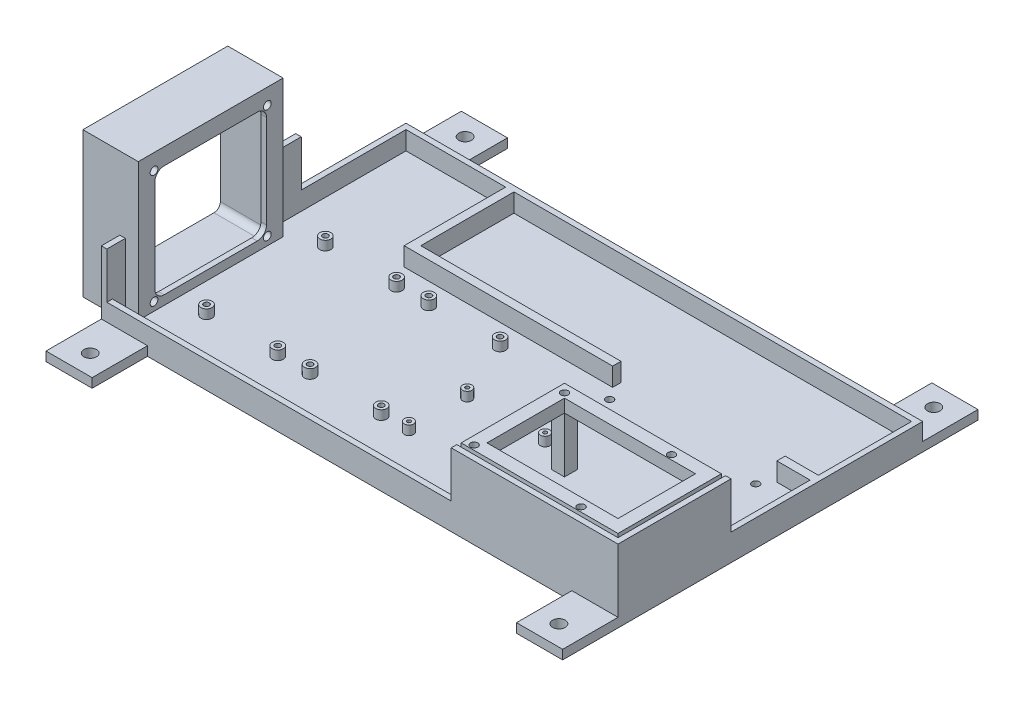
SolidWorks part; units mm, degrees
ref_plane "Front Plane" through (0, 0, 0) normal (0, 0, 1) x (1, 0, 0)
ref_plane "Top Plane" through (0, 0, 0) normal (0, 1, 0) x (1, 0, 0)
ref_plane "Right Plane" through (0, 0, 0) normal (1, 0, 0) x (0, 0, -1)
sketch "Sketch1" plane through (0, 0, 0) normal (0, 1, 0) x (1, 0, 0)
  line L1 (-140, -82.55) -> (140, -82.55)
  line L2 (-140, -82.55) -> (-140, 82.55)
  line L3 (-140, 82.55) -> (140, 82.55)
  line L4 (140, -82.55) -> (140, 82.55)
  line L5 (-140, -82.55) -> (140, 82.55) construction
  line L6 (-140, 82.55) -> (140, -82.55) construction
  point P0 (0, 0)
  dimension "D1" = 165.1
  dimension "D2" = 280
extrude "Floor" add sketch "Sketch1" along normal blind 4.3805
sketch "Sketch2" plane through (0, 4.3805, 0) normal (0, 1, 0) x (1, 0, 0)
  line L0 (137, -79.55) -> (137, 79.55)
  line L1 (137, 79.55) -> (-137, 79.55)
  line L2 (-137, 79.55) -> (-137, -79.55)
  line L3 (-137, -79.55) -> (137, -79.55)
  line L4 (140, -82.55) -> (140, 82.55)
  line L5 (140, 82.55) -> (-140, 82.55)
  line L6 (-140, 82.55) -> (-140, -82.55)
  line L7 (-140, -82.55) -> (140, -82.55)
  line L8 (140, -82.55) -> (140, 82.55)
  line L9 (140, 82.55) -> (-140, 82.55)
  line L10 (-140, 82.55) -> (-140, -82.55)
  line L11 (-140, -82.55) -> (140, -82.55)
  dimension "D1" = 0
  dimension "D2" = 3
extrude "Wall" add sketch "Sketch2" along normal blind 10
sketch "Sketch4" plane through (0, 4.3805, 0) normal (0, 1, 0) x (1, 0, 0)
  line L0 (130, -30.55) -> (59, -30.55)
  line L1 (137, -79.55) -> (52, -79.55)
  line L2 (137, -79.55) -> (137, -23.55)
  line L3 (137, -23.55) -> (52, -23.55)
  line L4 (52, -79.55) -> (52, -23.55)
  line L5 (59, -72.55) -> (59, -30.55)
  line L6 (130, -72.55) -> (59, -72.55)
  line L7 (130, -72.55) -> (130, -30.55)
  dimension "D1" = 85
  dimension "D2" = 56
  dimension "D3" = 7
extrude "Rpi stand" add sketch "Sketch4" along normal blind 7 from offset 30
sketch "Sketch7" plane through (0, 14.3805, 0) normal (0, 1, 0) x (1, 0, 0)
  line L0 (-137, 79.55) -> (-137, -79.55) construction
  line L1 (-140, -82.55) -> (-137, -82.55)
  line L2 (-140, -82.55) -> (-140, 22.7839)
  line L3 (-140, 22.7839) -> (-137, 22.7839)
  line L4 (-137, -82.55) -> (-137, 22.7839)
  line L5 (-137, -79.55) -> (137, -79.55) construction
  line L6 (140, -82.55) -> (49.6123, -82.55)
  line L7 (140, -82.55) -> (140, -79.55)
  line L8 (137, -79.55) -> (49.6123, -79.55)
  line L9 (49.6123, -82.55) -> (49.6123, -79.55)
  line L10 (137, -79.55) -> (137, 79.55) construction
  line L12 (140, -79.55) -> (140, -21.3069)
  line L13 (140, -21.3069) -> (137, -21.3069)
  line L14 (137, -79.55) -> (137, -21.3069)
  line L15 (-137, -79.55) -> (137, -79.55) construction
extrude "Temp support" add sketch "Sketch7" along normal blind 25
sketch "Sketch3" plane through (0, 0, 0) normal (0, 1, 0) x (1, 0, 0)
  line L0 (-127, 101.6) -> (127, 101.6) construction
  line L1 (-140, 82.55) -> (-115, 82.55)
  line L2 (-140, 82.55) -> (-140, 112.55)
  line L3 (-140, 112.55) -> (-115, 112.55)
  line L4 (-115, 82.55) -> (-115, 112.55)
  line L5 (140, 82.55) -> (115, 82.55)
  line L6 (140, 82.55) -> (140, 112.55)
  line L7 (140, 112.55) -> (115, 112.55)
  line L8 (115, 82.55) -> (115, 112.55)
  line L9 (-140, -82.55) -> (-115, -82.55)
  line L10 (-140, -82.55) -> (-140, -112.55)
  line L11 (-140, -112.55) -> (-115, -112.55)
  line L12 (-115, -82.55) -> (-115, -112.55)
  line L13 (140, -82.55) -> (115, -82.55)
  line L14 (140, -82.55) -> (140, -112.55)
  line L15 (140, -112.55) -> (115, -112.55)
  line L16 (115, -82.55) -> (115, -112.55)
  line L17 (127, 101.6) -> (127, -101.6) construction
  line L18 (127, -101.6) -> (-127, -101.6) construction
  line L19 (-127, -101.6) -> (-127, 101.6) construction
  line L20 (-140, 30.6215) -> (140, 30.6215) construction
  line L22 (140, -21.3069) -> (140, 82.55) construction
  line L23 (0, 101.6) -> (0, -101.6) construction
  line L24 (-140, 22.7839) -> (-140, -82.55) construction
  line L25 (140, -21.3069) -> (140, 82.55) construction
  line L26 (-137, -82.55) -> (49.6123, -82.55) construction
  circle A0 centre (-127, 101.6) radius 3.429
  circle A1 centre (127, 101.6) radius 3.429
  circle A2 centre (127, -101.6) radius 3.429
  circle A3 centre (-127, -101.6) radius 3.429
  point P28 (-127.5, -82.55)
  point P29 (-115, -97.55)
  point P30 (127.5, -82.55)
  point P31 (-115, 97.55)
  dimension "D5" = 6.858
  dimension "D1" = 25
  dimension "D2" = 25
  dimension "D3" = 30
  dimension "D4" = 30
  dimension "D6" = 203.2
  dimension "D7" = 254
extrude "Brackets" add sketch "Sketch3" along normal blind 5
sketch "Sketch5" plane through (-140, 0, 0) normal (-1, 0, 0) x (0, 0, 1)
  line L0 (-5.95, 78.8805) -> (72.55, 78.8805)
  line L1 (1.55, 4.3805) -> (65.05, 4.3805)
  line L2 (-1.95, 7.8805) -> (-1.95, 71.3805)
  line L3 (1.55, 74.8805) -> (65.05, 74.8805)
  line L4 (68.55, 7.8805) -> (68.55, 71.3805)
  line L5 (72.55, 0.3805) -> (72.55, 78.8805)
  line L6 (-5.95, 0.3805) -> (72.55, 0.3805)
  line L7 (-5.95, 0.3805) -> (-5.95, 78.8805)
  line L8 (-1.95, 4.3805) -> (68.55, 4.3805) construction
  line L9 (112.55, 5) -> (112.55, 0) construction
  line L10 (-1.95, 4.3805) -> (-1.95, 74.8805) construction
  line L11 (-79.55, 4.3805) -> (79.55, 4.3805) construction
  line L12 (68.55, 4.3805) -> (68.55, 74.8805) construction
  line L13 (-1.95, 74.8805) -> (68.55, 74.8805) construction
  arc A0 (1.55, 4.3805) -> (-1.95, 7.8805) centre (1.55, 7.8805) cw
  arc A1 (65.05, 4.3805) -> (68.55, 7.8805) centre (65.05, 7.8805) ccw
  arc A2 (65.05, 74.8805) -> (68.55, 71.3805) centre (65.05, 71.3805) cw
  arc A3 (-1.95, 71.3805) -> (1.55, 74.8805) centre (1.55, 71.3805) cw
  dimension "D4" = 3.5
  dimension "D1" = 70.5
  dimension "D2" = 70.5
  dimension "D5" = 40
  dimension "D3" = 4
extrude "Fan Holder" add sketch "Sketch5" along normal blind 20 and the other way blind 10
sketch "Sketch8" plane through (-140, 0, 0) normal (-1, 0, 0) x (0, 0, 1)
  line L4 (-1.95, 39.3805) -> (-1.95, 7.8805)
  line L5 (1.55, 4.3805) -> (65.05, 4.3805)
  line L6 (68.55, 7.8805) -> (68.55, 39.3805)
  line L7 (68.55, 39.3805) -> (-1.95, 39.3805)
  line L8 (-1.95, 39.3805) -> (-1.95, 7.8805)
  line L9 (1.55, 4.3805) -> (65.05, 4.3805)
  line L10 (68.55, 7.8805) -> (68.55, 39.3805)
  line L15 (68.55, 39.3805) -> (-1.95, 39.3805)
  arc A2 (-1.95, 7.8805) -> (1.55, 4.3805) centre (1.55, 7.8805) ccw
  arc A3 (-1.95, 7.8805) -> (1.55, 4.3805) centre (1.55, 7.8805) ccw
  arc A4 (65.05, 4.3805) -> (68.55, 7.8805) centre (65.05, 7.8805) ccw
  arc A5 (65.05, 4.3805) -> (68.55, 7.8805) centre (65.05, 7.8805) ccw
  dimension "D1" = 0
extrude "Fan hole" cut sketch "Sketch8" against normal up to next (3 mm away)
sketch "Sketch11" plane through (-130, 0, 0) normal (-1, 0, 0) x (0, 0, 1)
  line L0 (-5.95, 39.6305) -> (72.55, 39.6305) construction
  line L1 (33.3, 78.8805) -> (33.3, 0.3805) construction
  line L3 (2.6, 8.9305) -> (64, 8.9305) construction
  line L4 (-5.95, 78.8805) -> (-5.95, 0.3805)
  line L5 (-5.95, 0.3805) -> (72.55, 0.3805)
  line L6 (72.55, 0.3805) -> (72.55, 78.8805)
  line L7 (72.55, 78.8805) -> (-5.95, 78.8805)
  line L8 (-5.95, 78.8805) -> (-5.95, 0.3805)
  line L9 (-5.95, 0.3805) -> (72.55, 0.3805)
  line L10 (72.55, 0.3805) -> (72.55, 78.8805)
  line L11 (72.55, 78.8805) -> (-5.95, 78.8805)
  line L12 (2.6, 8.9305) -> (2.6, 70.3305) construction
  line L13 (2.6, 70.3305) -> (64, 70.3305) construction
  line L14 (64, 8.9305) -> (64, 70.3305) construction
  line L15 (2.6, 8.9305) -> (64, 70.3305) construction
  line L16 (3.05, 69.8805) -> (3.05, 9.3805)
  line L17 (3.05, 9.3805) -> (63.55, 9.3805)
  line L18 (63.55, 9.3805) -> (63.55, 69.8805)
  line L19 (63.55, 69.8805) -> (3.05, 69.8805)
  line L20 (3.05, 64.8805) -> (3.05, 14.3805)
  line L21 (8.05, 9.3805) -> (58.55, 9.3805)
  line L22 (63.55, 14.3805) -> (63.55, 64.8805)
  line L23 (58.55, 69.8805) -> (8.05, 69.8805)
  line L24 (2.6, 70.3305) -> (64, 8.9305) construction
  arc A0 (3.05, 14.3805) -> (8.05, 9.3805) centre (8.05, 14.3805) ccw
  arc A1 (58.55, 9.3805) -> (63.55, 14.3805) centre (58.55, 14.3805) ccw
  arc A2 (63.55, 64.8805) -> (58.55, 69.8805) centre (58.55, 64.8805) ccw
  arc A3 (3.05, 64.8805) -> (8.05, 69.8805) centre (8.05, 64.8805) cw
  circle A4 centre (2.6, 70.3305) radius 2.1
  circle A5 centre (64, 70.3305) radius 2.1
  circle A6 centre (64, 8.9305) radius 2.1
  circle A7 centre (2.6, 8.9305) radius 2.1
  point P24 (33.3, 39.6305)
  point P33 (0, 0)
  point P34 (33.3, 39.6305)
  dimension "D3" = 5
  dimension "D6" = 4.2
  dimension "D4" = 61.4
  dimension "D5" = 61.4
  dimension "D1" = 0
  dimension "D2" = 9
extrude "Boss-Extrude9" add sketch "Sketch11" along normal blind 3
sketch "Sketch12" plane through (0, 34.3805, 0) normal (0, -1, 0) x (1, 0, 0)
  line L1 (52, 23.55) -> (59, 23.55)
  line L2 (52, 23.55) -> (52, 30.55)
  line L3 (52, 30.55) -> (59, 30.55)
  line L4 (59, 23.55) -> (59, 30.55)
  dimension "D1" = 7
  dimension "D2" = 7
extrude "Boss-Extrude10" add sketch "Sketch12" along normal up to next
sketch "Sketch13" plane through (0, 4.3805, 0) normal (0, 1, 0) x (1, 0, 0)
  line L0 (-137, -79.55) -> (137, -79.55) construction
  line L1 (-137, -82.55) -> (-137, -72.55) construction
  line L2 (-114, -51.55) -> (-114, 12.85) construction
  line L3 (-114, 12.85) -> (-75.4, 12.85) construction
  line L4 (-114, -51.55) -> (-75.4, -51.55) construction
  line L5 (-75.4, 12.85) -> (-75.4, -51.55) construction
  line L6 (-75.4, 12.85) -> (-57.9, 12.85) construction
  line L7 (-57.9, 12.85) -> (-57.9, -51.55) construction
  line L8 (-57.9, -51.55) -> (-19.3, -51.55) construction
  line L9 (-19.3, -51.55) -> (-19.3, 12.85) construction
  line L10 (-19.3, 12.85) -> (-57.9, 12.85) construction
  line L11 (-75.4, -51.55) -> (-57.9, -51.55) construction
  line L12 (-19.3, -51.55) -> (-4.3, -51.55) construction
  line L13 (-4.3, -51.55) -> (-4.3, -19.95) construction
  line L14 (-4.3, -19.95) -> (37.87, -19.95) construction
  line L15 (37.87, -19.95) -> (37.87, -51.55) construction
  line L16 (37.87, -51.55) -> (-4.3, -51.55) construction
  line L17 (111.34, 79.55) -> (111.34, 18.05) construction
  line L19 (137, 79.55) -> (-137, 79.55) construction
  line L20 (137, -21.3069) -> (137, 79.55) construction
  line L21 (111.34, 18.05) -> (114.04, 18.05) construction
  line L22 (111.34, 18.05) -> (34.84, 18.05) construction
  circle A0 centre (-114, -51.55) radius 1.5
  circle A1 centre (-114, 12.85) radius 1.5
  circle A2 centre (-75.4, 12.85) radius 1.5
  circle A3 centre (-75.4, -51.55) radius 1.5
  circle A4 centre (-57.9, 12.85) radius 1.5
  circle A5 centre (-57.9, -51.55) radius 1.5
  circle A6 centre (-19.3, -51.55) radius 1.5
  circle A7 centre (-19.3, 12.85) radius 1.5
  circle A8 centre (-4.3, -51.55) radius 1
  circle A9 centre (-4.3, -19.95) radius 1
  circle A10 centre (37.87, -19.95) radius 1
  circle A11 centre (37.87, -51.55) radius 1
  circle A12 centre (114.04, 18.05) radius 2
  circle A13 centre (34.84, 18.05) radius 2
  circle A14 centre (-114, 12.85) radius 3
  circle A15 centre (-114, -51.55) radius 3
  circle A16 centre (-75.4, 12.85) radius 3
  circle A17 centre (-57.9, 12.85) radius 3
  circle A18 centre (-75.4, -51.55) radius 3
  circle A19 centre (-57.9, -51.55) radius 3
  circle A20 centre (-19.3, -51.55) radius 3
  circle A21 centre (-19.3, 12.85) radius 3
  circle A22 centre (-4.3, -51.55) radius 2.5
  circle A23 centre (-4.3, -19.95) radius 2.5
  circle A24 centre (37.87, -19.95) radius 2.5
  circle A25 centre (37.87, -51.55) radius 2.5
  point P6 (-137, -77.55)
  dimension "D1" = 28
  dimension "D2" = 23
  dimension "D3" = 3
  dimension "D6" = 3
  dimension "D7" = 3
  dimension "D8" = 3
  dimension "D11" = 3
  dimension "D12" = 3
  dimension "D13" = 3
  dimension "D14" = 3
  dimension "D16" = 2
  dimension "D18" = 2
  dimension "D20" = 2
  dimension "D21" = 2
  dimension "D25" = 4
  dimension "D27" = 4
  dimension "D4" = 64.4
  dimension "D5" = 38.6
  dimension "D9" = 17.5
  dimension "D10" = 38.6
  dimension "D15" = 15
  dimension "D17" = 31.6
  dimension "D19" = 42.17
  dimension "D22" = 61.5
  dimension "D23" = 25.66
  dimension "D24" = 2.7
  dimension "D26" = 76.5
  dimension "D28" = 1.5
extrude "Boss-Extrude12" add sketch "Sketch13" along normal blind 5 contours A1 | A16 A2 | A2 | A17 A4 | A4 | A14 A1 | A21 A7 | A7 | A15 A0 | A0 | A18 A3 | A3 | A19 A5 | A5 | A20 A6 | A6 | A22 A8 | A8 | A23 A9 | A9 | A24 A10 | A10 | A25 A11 | A11 region at (-114, 4.3805, 51.55) region at (-114, 4.3805, -12.85) region at (-75.4, 4.3805, -12.85) region at (-75.4, 4.3805, 51.55) region at (-57.9, 4.3805, -12.85) region at (-57.9, 4.3805, 51.55) region at (-19.3, 4.3805, 51.55) region at (-19.3, 4.3805, -12.85) region at (-4.3, 4.3805, 51.55) region at (-4.3, 4.3805, 19.95) region at (37.87, 4.3805, 19.95) region at (37.87, 4.3805, 51.55) region at (-116.9151, 4.3805, -12.85) region at (-116.9151, 4.3805, 51.55) region at (-78.3151, 4.3805, -12.85) region at (-60.8151, 4.3805, -12.85) region at (-78.3151, 4.3805, 51.55) region at (-60.8151, 4.3805, 51.55) region at (-22.2151, 4.3805, 51.55) region at (-22.2151, 4.3805, -12.85) region at (-6.7293, 4.3805, 51.55) region at (-6.7293, 4.3805, 19.95) region at (35.4407, 4.3805, 19.95) region at (35.4407, 4.3805, 51.55)
sketch "Sketch14" plane through (0, 4.3805, 0) normal (0, 1, 0) x (1, 0, 0)
  line L0 (137, 79.55) -> (-78, 79.55)
  line L1 (137, 79.55) -> (-137, 79.55) construction
  line L2 (-78, 79.55) -> (-78, 29.55)
  line L3 (-78, 29.55) -> (137, 29.55)
  line L4 (137, -79.55) -> (137, 79.55) construction
  line L5 (137, 29.55) -> (137, 79.55)
  dimension "D1" = 215
  dimension "D2" = 50
extrude "Cut-Extrude1" cut sketch "Sketch13<4>" against normal blind 5 from surface contours A1 | A0 | A3 | A5 | A2 | A4 | A7 | A9 | A8 | A6 | A11 | A10 starting at face at (-114, 9.3805, -9.85)
sketch "Sketch13<4>" plane through (0, 4.3805, 0) normal (0, 1, 0) x (1, 0, 0) same geometry as "Sketch13"
extrude "Cut-Extrude2" cut sketch "Sketch13<5>" against normal blind 3 contours A13 | A12
sketch "Sketch13<5>" plane through (0, 4.3805, 0) normal (0, 1, 0) x (1, 0, 0) same geometry as "Sketch13"
sketch "Sketch16" plane through (0, 4.3805, 0) normal (0, 1, 0) x (1, 0, 0)
  line L0 (-83, 79.55) -> (-83, 24.55)
  line L1 (-83, 24.55) -> (30, 24.55)
  line L2 (-78.5, 79.55) -> (-78.5, 29.05)
  line L3 (-78.5, 29.05) -> (30, 29.05)
  line L10 (-78, 79.55) -> (-78, 29.55) construction
  line L11 (-78, 29.55) -> (29.1074, 29.55) construction
  line L12 (119, 24.55) -> (137, 24.55)
  line L13 (119, 29.55) -> (137, 29.55) construction
  line L14 (-83, 24.55) -> (137, 24.55) construction
  line L15 (119, 29.05) -> (137, 29.05)
  line L16 (-78, 29.55) -> (137, 29.55) construction
  line L17 (-78.5, 79.55) -> (-83, 79.55)
  line L18 (119, 29.05) -> (119, 24.55)
  line L19 (137, -21.3069) -> (137, 79.55) construction
  line L20 (30, 24.55) -> (30, 29.05)
  line L21 (-78.5, 29.05) -> (29.1074, 29.05) construction
  line L22 (137, 24.55) -> (137, 29.05)
  line L25 (-78, 29.55) -> (137, 29.55)
  line L26 (137, 29.55) -> (137, 79.55)
  line L27 (137, 79.55) -> (-78, 79.55)
  line L28 (-78, 79.55) -> (-78, 29.55)
  line L29 (-78, 29.55) -> (137, 29.55) construction
  line L30 (137, 29.55) -> (137, 79.55) construction
  line L31 (137, 79.55) -> (-78, 79.55) construction
  line L32 (-78, 79.55) -> (-78, 29.55) construction
  dimension "D3" = 0.5
  dimension "D4" = 18
  dimension "D5" = 113
  dimension "D1" = 0
  dimension "D2" = 5
extrude "Boss-Extrude11" add sketch "Sketch16" along normal blind 10 contours L2 L3 L20 L1 L0 L17 | L12 L22 L15 L18
sketch "Sketch17" plane through (0, 41.3805, 0) normal (0, 1, 0) x (1, 0, 0)
  circle A0 centre (56.5, -28.05) radius 2
  circle A1 centre (114.5, -28.05) radius 2
  circle A2 centre (114.5, -77.05) radius 2
  circle A3 centre (56.5, -77.05) radius 2
  dimension "D1" = 4
extrude "Cut-Extrude3" cut sketch "Sketch17" against normal blind 3
equation "\"D2@Sketch3\"=\"D1@Sketch3\""
equation "\"D4@Sketch3\"=\"D3@Sketch3\""
